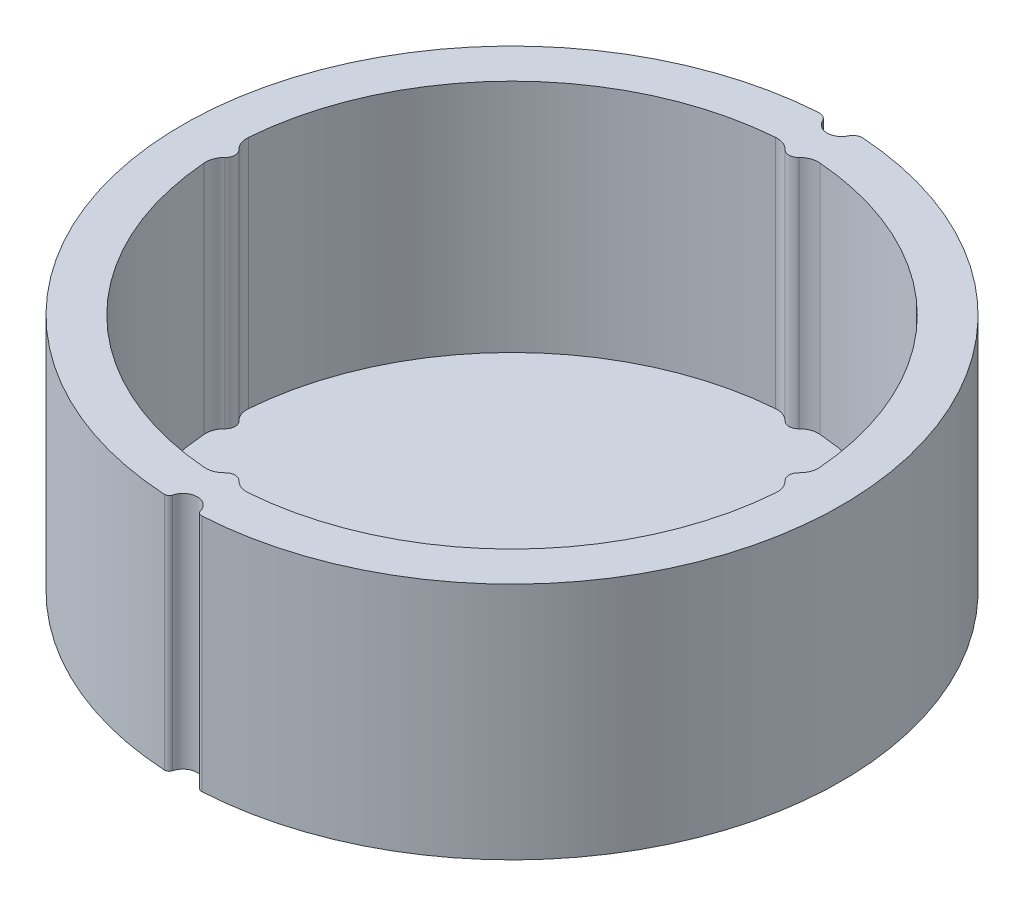
SolidWorks part; units mm, degrees
ref_plane "Front Plane" through (0, 0, 0) normal (0, 0, 1) x (1, 0, 0)
ref_plane "Top Plane" through (0, 0, 0) normal (0, 1, 0) x (1, 0, 0)
ref_plane "Right Plane" through (0, 0, 0) normal (1, 0, 0) x (0, 0, -1)
sketch "Sketch1" plane through (0, 0, 0) normal (0, 1, 0) x (1, 0, 0)
  line L3 (0, 0.002) -> (0, 3.7877) construction
  line L4 (0, 3.7877) -> (2.417, 3.7877)
  line L5 (0, 3.7877) -> (-2.417, 3.7877)
  arc A0 (1.9642, -34.442) -> (34.1982, 4.5552) centre (0, 0.002) ccw
  arc A2 (-2.417, 3.7877) -> (2.417, 3.7877) centre (0, 0.002) ccw
  circle A3 centre (0, 0.002) radius 34.5 construction
  arc A7 (-1.3541, 33.8562) -> (1.3541, 33.8562) centre (0, 34.5015) ccw
  arc A8 (34.1982, 4.5552) -> (2.3241, 34.4236) centre (0, 0.002) ccw
  arc A9 (-2.3241, 34.4236) -> (-34.1982, 4.5552) centre (0, 0.002) ccw
  arc A10 (-34.1982, 4.5552) -> (-1.9642, -34.442) centre (0, 0.002) ccw
  arc A11 (1.3541, 33.8562) -> (2.3241, 34.4236) centre (2.2568, 33.4259) cw
  arc A12 (-1.3541, 33.8562) -> (-2.3241, 34.4236) centre (-2.2568, 33.4259) ccw
  arc A13 (1.4518, -34.0686) -> (-1.4518, -34.0686) centre (0, -34.4457) ccw
  arc A14 (1.4518, -34.0686) -> (1.9642, -34.442) centre (1.9358, -33.9428) ccw
  arc A15 (-1.4518, -34.0686) -> (-1.9642, -34.442) centre (-1.9358, -33.9428) cw
  point P15 (1.4997, 34.4694)
  dimension "D2" = 4.834
  dimension "D3" = 4.4915
  dimension "D4" = 34.5
  dimension "D5" = 1
  dimension "D6" = 1.5
  dimension "D7" = 0.5
  dimension "D11" = 1.4997
sketch "Sketch2" plane through (0, 0, 0) normal (0, 1, 0) x (1, 0, 0)
  arc A0 (-29.9107, -2.3128) -> (-2.3128, -29.9107) centre (0, 0) ccw
  arc A1 (-0.7195, 29.3056) -> (0.7195, 29.3056) centre (0, 30) ccw
  arc A2 (29.3056, 0.7195) -> (29.3056, -0.7195) centre (30, 0) ccw
  arc A3 (0.7195, -29.3056) -> (-0.7195, -29.3056) centre (0, -30) ccw
  arc A4 (-29.3056, -0.7195) -> (-29.3056, 0.7195) centre (-30, 0) ccw
  arc A5 (-2.3128, 29.9107) -> (-29.9107, 2.3128) centre (0, 0) ccw
  arc A6 (29.9107, 2.3128) -> (2.3128, 29.9107) centre (0, 0) ccw
  arc A7 (2.3128, -29.9107) -> (29.9107, -2.3128) centre (0, 0) ccw
  arc A8 (-29.3056, -0.7195) -> (-29.9107, -2.3128) centre (-27.9167, -2.1586) ccw
  arc A9 (-29.3056, 0.7195) -> (-29.9107, 2.3128) centre (-27.9167, 2.1586) cw
  arc A10 (0.7195, -29.3056) -> (2.3128, -29.9107) centre (2.1586, -27.9167) ccw
  arc A11 (-0.7195, -29.3056) -> (-2.3128, -29.9107) centre (-2.1586, -27.9167) cw
  arc A12 (29.3056, 0.7195) -> (29.9107, 2.3128) centre (27.9167, 2.1586) ccw
  arc A13 (29.3056, -0.7195) -> (29.9107, -2.3128) centre (27.9167, -2.1586) cw
  arc A14 (0.7195, 29.3056) -> (2.3128, 29.9107) centre (2.1586, 27.9167) cw
  arc A15 (-0.7195, 29.3056) -> (-2.3128, 29.9107) centre (-2.1586, 27.9167) ccw
  point P21 (0.9999, -29.9833)
  point P26 (29.9833, 0.9999)
  point P33 (-0.9999, 29.9833)
  dimension "D1" = 30
  dimension "D2" = 1
  dimension "D3" = 1
  dimension "D4" = 1
  dimension "D5" = 1
  dimension "D6" = 2
extrude "Boss-Extrude1" add sketch "Sketch1" along normal blind 25 contours A10 A0 A8 A7 A9 A2 L5 L4 region at (2.2155, 0, 33.5591)
extrude "Cut-Extrude2" cut sketch "Sketch2" along normal through all
extrude "Boss-Extrude2" add sketch "Sketch2<2>" along normal blind 0.4
sketch "Sketch2<2>" plane through (0, 0, 0) normal (0, 1, 0) x (1, 0, 0) same geometry as "Sketch2"
